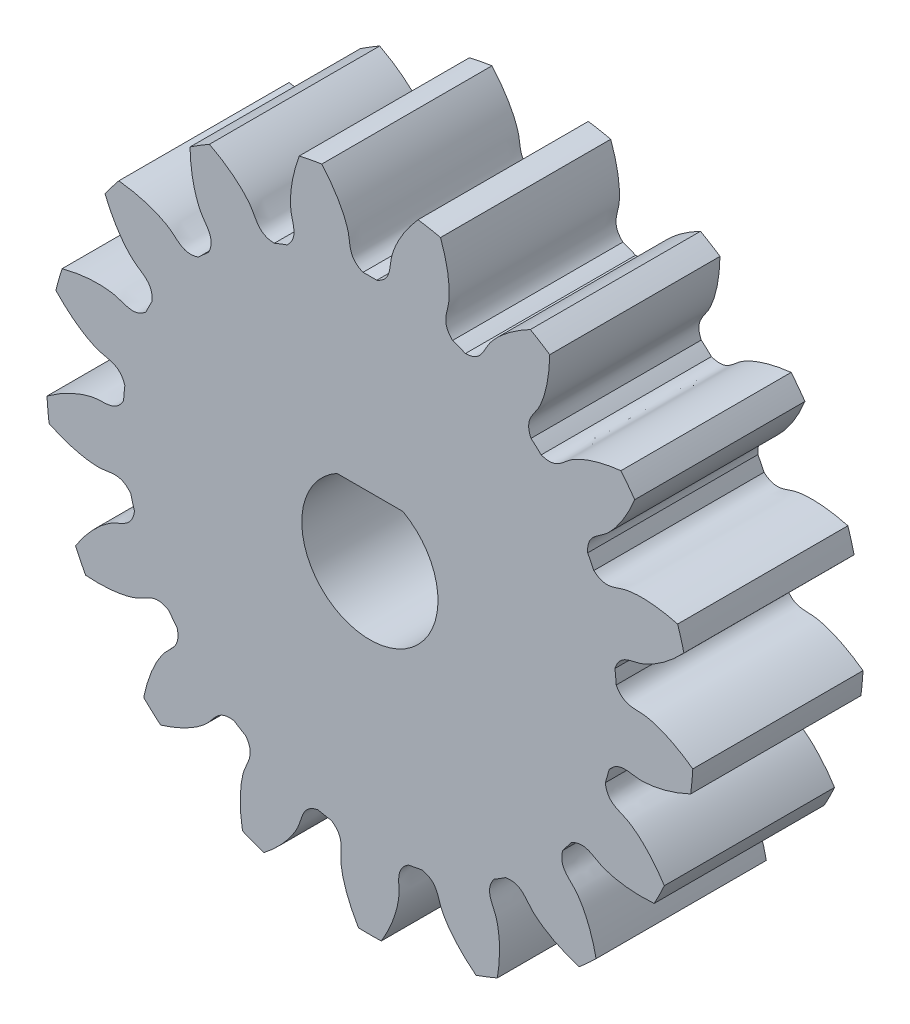
SolidWorks part; units mm, degrees
ref_plane "前视基准面" through (0, 0, 0) normal (0, 0, 1) x (1, 0, 0)
ref_plane "上视基准面" through (0, 0, 0) normal (0, 1, 0) x (1, 0, 0)
ref_plane "右视基准面" through (0, 0, 0) normal (1, 0, 0) x (0, 0, -1)
sketch "草图1" plane through (0, 0, 0) normal (0, 0, 1) x (1, 0, 0)
  circle A0 centre (0, 0) radius 19
extrude "凸台-拉伸1" add sketch "草图1" along normal blind 10
ref_axis "基准轴1" through (0, 0, -1.5) along (0, 0, 1)
sketch "草图2" plane through (0, 0, 0) normal (0, 0, 1) x (1, 0, 0)
  line L0 (0, 0) -> (0, 19) construction
  circle A0 centre (0, 0) radius 19 construction
  arc A1 (0.4034, 14.4944) -> (-0.4034, 14.4944) centre (0, 0) ccw
  arc A2 (6.2313, 21.4814) -> (-6.2313, 21.4814) centre (0, 0) ccw
  spline S0 degree 3 poles (0.4034, 14.4944) (1.2558, 14.8496) (1.1324, 15.5096) (1.2766, 16.1296) (1.29, 16.1823) (1.306, 16.2408) (1.3251, 16.3052) (1.3474, 16.3752) (1.3731, 16.4508) (1.4025, 16.5319) (1.4359, 16.6184) (1.4733, 16.7101) (1.5152, 16.8068) (1.5616, 16.9086) (1.6128, 17.0151) (1.669, 17.1264) (1.7304, 17.2421) (1.7972, 17.3621) (1.8696, 17.4863) (1.9478, 17.6145) (2.032, 17.7465) (2.1224, 17.8821) (2.2191, 18.0211) (2.3223, 18.1634) (2.4322, 18.3086) (2.5489, 18.4566) (2.6727, 18.6072) (2.8035, 18.7601) (2.9417, 18.9152) (3.0873, 19.0722) (3.2404, 19.2308) (3.4012, 19.3908) (3.5698, 19.552) (3.7462, 19.7141) (3.9307, 19.8769) (4.1233, 20.0401) (4.324, 20.2035) (4.533, 20.3667) (4.7503, 20.5295) (4.9761, 20.6917) (5.2103, 20.853) (5.453, 21.0131) (5.7916, 21.2269) (6.0532, 21.3811) (6.2313, 21.4814) knots 0 0 0 0 0.193883 0.199024 0.204851 0.211363 0.21856 0.226443 0.235011 0.244265 0.254205 0.264829 0.27614 0.288136 0.300817 0.314184 0.328236 0.342973 0.358397 0.374505 0.391299 0.408779 0.426944 0.445795 0.465331 0.485552 0.506459 0.528051 0.550329 0.573293 0.596941 0.621276 0.646296 0.672001 0.698392 0.725468 0.753229 0.781677 0.810809 0.840627 0.871131 0.90232 0.934195 1 1 1 1
  spline S1 degree 3 poles (-0.4034, 14.4944) (-1.2558, 14.8496) (-1.1324, 15.5096) (-1.2766, 16.1296) (-1.29, 16.1823) (-1.306, 16.2408) (-1.3251, 16.3052) (-1.3474, 16.3752) (-1.3731, 16.4508) (-1.4025, 16.5319) (-1.4359, 16.6184) (-1.4733, 16.7101) (-1.5152, 16.8068) (-1.5616, 16.9086) (-1.6128, 17.0151) (-1.669, 17.1264) (-1.7304, 17.2421) (-1.7972, 17.3621) (-1.8696, 17.4863) (-1.9478, 17.6145) (-2.032, 17.7465) (-2.1224, 17.8821) (-2.2191, 18.0211) (-2.3223, 18.1634) (-2.4322, 18.3086) (-2.5489, 18.4566) (-2.6727, 18.6072) (-2.8035, 18.7601) (-2.9417, 18.9152) (-3.0873, 19.0722) (-3.2404, 19.2308) (-3.4012, 19.3908) (-3.5698, 19.552) (-3.7462, 19.7141) (-3.9307, 19.8769) (-4.1233, 20.0401) (-4.324, 20.2035) (-4.533, 20.3667) (-4.7503, 20.5295) (-4.9761, 20.6917) (-5.2103, 20.853) (-5.453, 21.0131) (-5.7916, 21.2269) (-6.0532, 21.3811) (-6.2313, 21.4814) knots 0 0 0 0 0.193883 0.199024 0.204851 0.211363 0.21856 0.226443 0.235011 0.244265 0.254205 0.264829 0.27614 0.288136 0.300817 0.314184 0.328236 0.342973 0.358397 0.374505 0.391299 0.408779 0.426944 0.445795 0.465331 0.485552 0.506459 0.528051 0.550329 0.573293 0.596941 0.621276 0.646296 0.672001 0.698392 0.725468 0.753229 0.781677 0.810809 0.840627 0.871131 0.90232 0.934195 1 1 1 1
extrude "切除-拉伸1" cut sketch "草图2" along normal through all
pattern_circular "阵列(圆周)1" count 17 every 21.176 about axis through (0, 0, -1.5) along (0, 0, 1) of "切除-拉伸1"
sketch "草图3" plane through (0, 0, 0) normal (0, 0, 1) x (1, 0, 0)
  circle A0 centre (0, 0) radius 17 construction
  dimension "Dn" = 34
sketch "草图4" plane through (0, 0, 10) normal (0, 0, 1) x (1, 0, 0)
  line L0 (-1.9365, 3.5) -> (1.9365, 3.5)
  arc A0 (-1.9365, 3.5) -> (1.9365, 3.5) centre (0, 0) ccw
  dimension "D1" = 8
  dimension "D2" = 3.5
extrude "切除-拉伸2" cut sketch "草图4" against normal up to next
